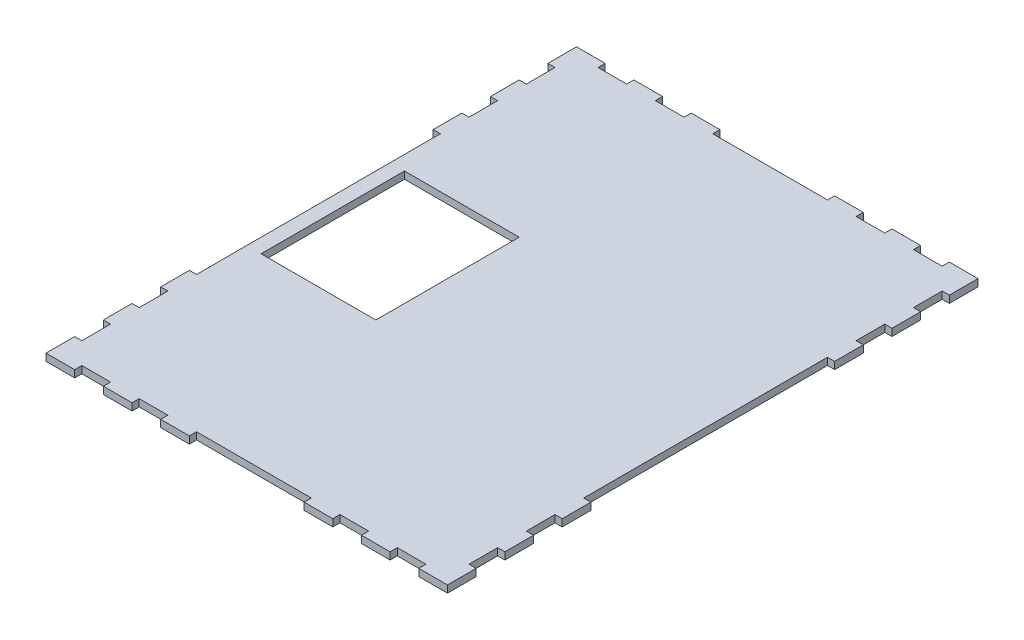
SolidWorks part; units mm, degrees
material "Acrylic (Medium-high impact)"
ref_plane "Front Plane" through (0, 0, 0) normal (0, 0, 1) x (1, 0, 0)
ref_plane "Top Plane" through (0, 0, 0) normal (0, 1, 0) x (1, 0, 0)
ref_plane "Right Plane" through (0, 0, 0) normal (1, 0, 0) x (0, 0, -1)
sketch "Sketch1" plane through (0, 0, 0) normal (0, 1, 0) x (1, 0, 0)
  line L0 (0, 209.55) -> (0, 196.85)
  line L1 (0, 0) -> (177.8, 0)
  line L2 (0, 0) -> (0, 234.95)
  line L3 (0, 234.95) -> (177.8, 234.95)
  line L4 (177.8, 0) -> (177.8, 234.95)
  line L5 (0, 234.95) -> (3.175, 234.95)
  line L6 (0, 234.95) -> (0, 0)
  line L7 (0, 0) -> (3.175, 0)
  line L8 (3.175, 234.95) -> (3.175, 0)
  line L9 (177.8, 234.95) -> (174.625, 234.95)
  line L10 (177.8, 234.95) -> (177.8, 0)
  line L11 (177.8, 0) -> (174.625, 0)
  line L12 (174.625, 234.95) -> (174.625, 0)
  line L13 (0, 234.95) -> (3.175, 234.95)
  line L14 (0, 234.95) -> (0, 222.25)
  line L15 (0, 222.25) -> (3.175, 222.25)
  line L16 (3.175, 234.95) -> (3.175, 222.25)
  line L17 (0, 209.55) -> (3.175, 209.55)
  line L18 (3.175, 209.55) -> (3.175, 196.85)
  line L19 (0, 196.85) -> (3.175, 196.85)
  line L20 (0, 184.15) -> (0, 171.45)
  line L21 (0, 184.15) -> (3.175, 184.15)
  line L22 (3.175, 184.15) -> (3.175, 171.45)
  line L23 (0, 171.45) -> (3.175, 171.45)
  line L24 (0, 117.475) -> (177.8, 117.475) construction
  line L25 (88.9, 234.95) -> (88.9, 0) construction
  line L26 (177.8, 171.45) -> (174.625, 171.45)
  line L27 (174.625, 184.15) -> (174.625, 171.45)
  line L28 (177.8, 184.15) -> (174.625, 184.15)
  line L29 (177.8, 184.15) -> (177.8, 171.45)
  line L30 (177.8, 196.85) -> (174.625, 196.85)
  line L31 (174.625, 209.55) -> (174.625, 196.85)
  line L32 (177.8, 209.55) -> (174.625, 209.55)
  line L33 (174.625, 234.95) -> (174.625, 222.25)
  line L34 (177.8, 222.25) -> (174.625, 222.25)
  line L35 (177.8, 234.95) -> (177.8, 222.25)
  line L36 (177.8, 234.95) -> (174.625, 234.95)
  line L37 (177.8, 234.95) -> (177.8, 0)
  line L38 (177.8, 234.95) -> (174.625, 234.95)
  line L39 (177.8, 209.55) -> (177.8, 196.85)
  line L40 (177.8, 25.4) -> (177.8, 38.1)
  line L41 (177.8, 0) -> (174.625, 0)
  line L42 (177.8, 0) -> (174.625, 0)
  line L43 (177.8, 0) -> (177.8, 12.7)
  line L44 (177.8, 12.7) -> (174.625, 12.7)
  line L45 (174.625, 0) -> (174.625, 12.7)
  line L46 (177.8, 25.4) -> (174.625, 25.4)
  line L47 (174.625, 25.4) -> (174.625, 38.1)
  line L48 (177.8, 38.1) -> (174.625, 38.1)
  line L49 (177.8, 50.8) -> (177.8, 63.5)
  line L50 (177.8, 50.8) -> (174.625, 50.8)
  line L51 (174.625, 50.8) -> (174.625, 63.5)
  line L52 (177.8, 63.5) -> (174.625, 63.5)
  line L53 (0, 63.5) -> (3.175, 63.5)
  line L54 (3.175, 50.8) -> (3.175, 63.5)
  line L55 (0, 50.8) -> (3.175, 50.8)
  line L56 (0, 50.8) -> (0, 63.5)
  line L57 (0, 38.1) -> (3.175, 38.1)
  line L58 (3.175, 25.4) -> (3.175, 38.1)
  line L59 (0, 25.4) -> (3.175, 25.4)
  line L60 (3.175, 0) -> (3.175, 12.7)
  line L61 (0, 12.7) -> (3.175, 12.7)
  line L62 (0, 0) -> (0, 12.7)
  line L63 (0, 0) -> (3.175, 0)
  line L64 (177.8, 0) -> (174.625, 0)
  line L65 (0, 0) -> (3.175, 0)
  line L66 (0, 0) -> (177.8, 0)
  line L67 (0, 25.4) -> (0, 38.1)
  dimension "D1" = 234.95
  dimension "D2" = 177.8
  dimension "D3" = 3.175
  dimension "D4" = 3.175
  dimension "D5" = 12.7
  dimension "D6" = 3.175
  dimension "D7" = 3
extrude "Boss-Extrude1" add sketch "Sketch1" along normal blind 3.175 contours L6 L55 L8 L53 | L6 L59 L8 L57 | L61 L2 L1 L8 | L6 L23 L8 L21 | L0 L19 L8 L17 | L6 L15 L8 L3 | L4 L44 L12 L1 | L37 L48 L12 L46 | L37 L52 L12 L50 | L34 L10 L3 L12 | L10 L32 L12 L30 | L10 L28 L12 L26 | L52 L12 L26 L27 L28 L30 L31 L32 L34 L33 L3 L8 L1 L45 L44 L46 L47 L48 L50 L51 region at (1.5875, 0, -203.2) region at (1.5875, 0, -228.6) region at (88.9, 0, -117.475) region at (1.5875, 0, -177.8) region at (1.5875, 0, -57.15) region at (176.2125, 0, -228.6) region at (1.5875, 0, -31.75) region at (176.2125, 0, -203.2) region at (1.5875, 0, -6.35) region at (176.2125, 0, -177.8) region at (176.2125, 0, -57.15) region at (176.2125, 0, -6.35) region at (176.2125, 0, -31.75)
sketch "Sketch5" plane through (0, 3.175, 0) normal (0, 1, 0) x (1, 0, 0)
  line L0 (88.9, 0) -> (88.9, 18.3402) construction
  line L1 (0, 0) -> (177.8, 0) construction
  line L3 (0, 0) -> (12.7, 0)
  line L4 (0, 0) -> (0, 3.175)
  line L5 (0, 3.175) -> (12.7, 3.175)
  line L6 (12.7, 0) -> (12.7, 3.175)
  line L10 (25.4, 3.175) -> (38.1, 3.175)
  line L11 (25.4, 0) -> (38.1, 0)
  line L12 (38.1, 0) -> (38.1, 3.175)
  line L13 (25.4, 0) -> (25.4, 3.175)
  line L14 (50.8, 3.175) -> (63.5, 3.175)
  line L15 (50.8, 0) -> (63.5, 0)
  line L16 (63.5, 0) -> (63.5, 3.175)
  line L17 (50.8, 0) -> (50.8, 3.175)
  line L18 (0, 3.175) -> (177.8, 3.175)
  line L19 (127, 0) -> (127, 3.175)
  line L20 (114.3, 0) -> (114.3, 3.175)
  line L21 (127, 0) -> (114.3, 0)
  line L22 (127, 3.175) -> (114.3, 3.175)
  line L23 (152.4, 0) -> (152.4, 3.175)
  line L24 (139.7, 0) -> (139.7, 3.175)
  line L25 (152.4, 0) -> (139.7, 0)
  line L26 (152.4, 3.175) -> (139.7, 3.175)
  line L27 (165.1, 0) -> (165.1, 3.175)
  line L28 (177.8, 3.175) -> (165.1, 3.175)
  line L29 (177.8, 0) -> (177.8, 3.175)
  line L30 (177.8, 0) -> (165.1, 0)
  line L63 (0, 63.5) -> (0, 50.8)
  line L64 (0, 50.8) -> (3.175, 50.8)
  line L65 (3.175, 50.8) -> (3.175, 38.1)
  line L66 (3.175, 38.1) -> (0, 38.1)
  line L67 (0, 38.1) -> (0, 25.4)
  line L68 (0, 25.4) -> (3.175, 25.4)
  line L69 (3.175, 25.4) -> (3.175, 12.7)
  line L70 (3.175, 12.7) -> (0, 12.7)
  line L71 (0, 12.7) -> (0, 0)
  line L72 (0, 0) -> (177.8, 0)
  line L73 (177.8, 0) -> (177.8, 12.7)
  line L74 (177.8, 12.7) -> (174.625, 12.7)
  line L75 (174.625, 12.7) -> (174.625, 25.4)
  line L76 (174.625, 25.4) -> (177.8, 25.4)
  line L77 (177.8, 25.4) -> (177.8, 38.1)
  line L78 (177.8, 38.1) -> (174.625, 38.1)
  line L79 (174.625, 38.1) -> (174.625, 50.8)
  line L80 (174.625, 50.8) -> (177.8, 50.8)
  line L81 (177.8, 50.8) -> (177.8, 63.5)
  line L82 (177.8, 63.5) -> (174.625, 63.5)
  line L83 (174.625, 63.5) -> (174.625, 171.45)
  line L84 (174.625, 171.45) -> (177.8, 171.45)
  line L85 (177.8, 171.45) -> (177.8, 184.15)
  line L86 (177.8, 184.15) -> (174.625, 184.15)
  line L87 (174.625, 184.15) -> (174.625, 196.85)
  line L88 (174.625, 196.85) -> (177.8, 196.85)
  line L89 (177.8, 196.85) -> (177.8, 209.55)
  line L90 (177.8, 209.55) -> (174.625, 209.55)
  line L91 (174.625, 209.55) -> (174.625, 222.25)
  line L92 (174.625, 222.25) -> (177.8, 222.25)
  line L93 (177.8, 222.25) -> (177.8, 234.95)
  line L94 (177.8, 234.95) -> (0, 234.95)
  line L95 (0, 234.95) -> (0, 222.25)
  line L96 (0, 222.25) -> (3.175, 222.25)
  line L97 (3.175, 222.25) -> (3.175, 209.55)
  line L98 (3.175, 209.55) -> (0, 209.55)
  line L99 (0, 209.55) -> (0, 196.85)
  line L100 (0, 196.85) -> (3.175, 196.85)
  line L101 (3.175, 196.85) -> (3.175, 184.15)
  line L102 (3.175, 184.15) -> (0, 184.15)
  line L103 (0, 184.15) -> (0, 171.45)
  line L104 (0, 171.45) -> (3.175, 171.45)
  line L105 (3.175, 171.45) -> (3.175, 63.5)
  line L106 (3.175, 63.5) -> (0, 63.5)
  line L107 (0, 63.5) -> (0, 50.8)
  line L108 (0, 50.8) -> (3.175, 50.8)
  line L109 (3.175, 50.8) -> (3.175, 38.1)
  line L110 (3.175, 38.1) -> (0, 38.1)
  line L111 (0, 38.1) -> (0, 25.4)
  line L112 (0, 25.4) -> (3.175, 25.4)
  line L113 (3.175, 25.4) -> (3.175, 12.7)
  line L114 (3.175, 12.7) -> (0, 12.7)
  line L115 (0, 12.7) -> (0, 0)
  line L116 (0, 0) -> (177.8, 0)
  line L117 (177.8, 0) -> (177.8, 12.7)
  line L118 (177.8, 12.7) -> (174.625, 12.7)
  line L119 (174.625, 12.7) -> (174.625, 25.4)
  line L120 (174.625, 25.4) -> (177.8, 25.4)
  line L121 (177.8, 25.4) -> (177.8, 38.1)
  line L122 (177.8, 38.1) -> (174.625, 38.1)
  line L123 (174.625, 38.1) -> (174.625, 50.8)
  line L124 (174.625, 50.8) -> (177.8, 50.8)
  line L125 (177.8, 50.8) -> (177.8, 63.5)
  line L126 (177.8, 63.5) -> (174.625, 63.5)
  line L127 (174.625, 63.5) -> (174.625, 171.45)
  line L128 (174.625, 171.45) -> (177.8, 171.45)
  line L129 (177.8, 171.45) -> (177.8, 184.15)
  line L130 (177.8, 184.15) -> (174.625, 184.15)
  line L131 (174.625, 184.15) -> (174.625, 196.85)
  line L132 (174.625, 196.85) -> (177.8, 196.85)
  line L133 (177.8, 196.85) -> (177.8, 209.55)
  line L134 (177.8, 209.55) -> (174.625, 209.55)
  line L135 (174.625, 209.55) -> (174.625, 222.25)
  line L136 (174.625, 222.25) -> (177.8, 222.25)
  line L137 (177.8, 222.25) -> (177.8, 234.95)
  line L138 (177.8, 234.95) -> (0, 234.95)
  line L139 (0, 234.95) -> (0, 222.25)
  line L140 (0, 222.25) -> (3.175, 222.25)
  line L141 (3.175, 222.25) -> (3.175, 209.55)
  line L142 (3.175, 209.55) -> (0, 209.55)
  line L143 (0, 209.55) -> (0, 196.85)
  line L144 (0, 196.85) -> (3.175, 196.85)
  line L145 (3.175, 196.85) -> (3.175, 184.15)
  line L146 (3.175, 184.15) -> (0, 184.15)
  line L147 (0, 184.15) -> (0, 171.45)
  line L148 (0, 171.45) -> (3.175, 171.45)
  line L149 (3.175, 171.45) -> (3.175, 63.5)
  line L150 (3.175, 63.5) -> (0, 63.5)
  point P22 (88.9, 3.175)
  dimension "D1" = 3.175
  dimension "D2" = 12.7
  dimension "D4" = 0
  dimension "D3" = 3
extrude "Cut-Extrude4" cut sketch "Sketch5" against normal blind 7.62 contours L6 L116 L13 L18 | L12 L116 L17 L18 | L116 L0 L18 L16 | L0 L116 L20 L18 | L19 L116 L24 L18 | L23 L116 L27 L18 region at (76.2, 3.175, -1.5875) region at (101.6, 3.175, -1.5875) region at (44.45, 3.175, -1.5875) region at (133.35, 3.175, -1.5875) region at (19.05, 3.175, -1.5875) region at (158.75, 3.175, -1.5875)
ref_plane "Plane2" through (0, 0, -117.475) normal (0, 0, 1) x (1, 0, 0)
mirror "Mirror1" about plane through (0, 0, -117.475) normal (0, 0, 1) of "Cut-Extrude4"
sketch "Sketch7" plane through (0, 3.175, 0) normal (0, 1, 0) x (1, 0, 0)
  line L0 (3.175, 117.475) -> (174.625, 117.475) construction
  line L1 (3.175, 171.45) -> (3.175, 63.5) construction
  line L2 (174.625, 171.45) -> (174.625, 63.5) construction
  line L3 (3.175, 117.475) -> (9.525, 117.475) construction
  line L4 (9.525, 117.475) -> (9.525, 149.225)
  line L6 (9.525, 149.225) -> (60.325, 149.225)
  line L7 (9.525, 149.225) -> (9.525, 85.725)
  line L8 (9.525, 85.725) -> (60.325, 85.725)
  line L9 (60.325, 149.225) -> (60.325, 85.725)
  dimension "D1" = 6.35
  dimension "D2" = 31.75
  dimension "D3" = 63.5
  dimension "D4" = 50.8
extrude "Cut-Extrude5" cut sketch "Sketch7" against normal blind 7.62 contours L6 L9 L8 L7
